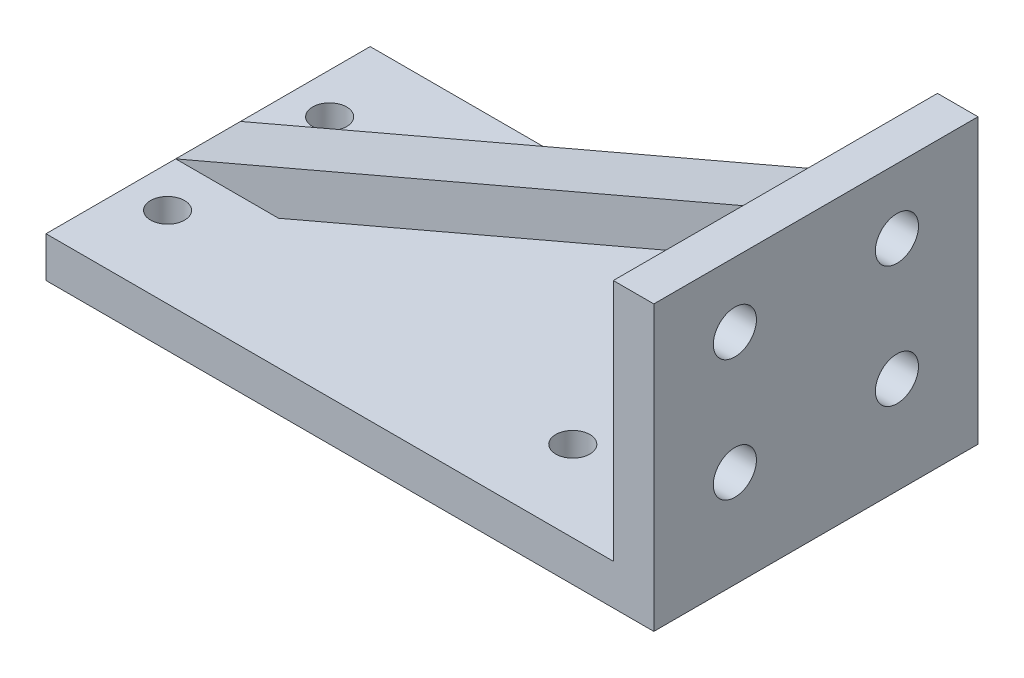
SolidWorks part; units mm, degrees
ref_plane "Front Plane" through (0, 0, 0) normal (0, 0, 1) x (1, 0, 0)
ref_plane "Top Plane" through (0, 0, 0) normal (0, 1, 0) x (1, 0, 0)
ref_plane "Right Plane" through (0, 0, 0) normal (1, 0, 0) x (0, 0, -1)
sketch "Sketch3" plane through (0, 0, 0) normal (0, 0, 1) x (1, 0, 0)
  line L0 (0, 6.35) -> (88.9, 44.45)
  line L1 (0, 0) -> (95.25, 0)
  line L2 (0, 0) -> (0, 6.35)
  line L3 (16.1201, 6.35) -> (88.9, 6.35)
  line L4 (95.25, 0) -> (95.25, 6.35)
  line L5 (95.25, 0) -> (88.9, 0)
  line L6 (95.25, 0) -> (95.25, 44.45)
  line L7 (95.25, 44.45) -> (88.9, 44.45)
  line L8 (88.9, 6.35) -> (88.9, 37.5414)
  line L9 (16.1201, 6.35) -> (88.9, 37.5414)
  line L10 (2.5014, 0.5134) -> (91.4014, 38.6134) construction
  dimension "D1" = 6.35
  dimension "D2" = 95.25
  dimension "D3" = 6.35
  dimension "D4" = 44.45
  dimension "D5" = 88.9
  dimension "D6" = 6.35
  dimension "D7" = 156.801
  dimension "D8" = 6.35
extrude "Boss-Extrude1" add sketch "Sketch3" along normal blind 50.8 contours L8 L3 L2 L1 L4 L6 L7 region at (44.8641, 24.4339, 0)
sketch "Sketch4" plane through (0, 0, 0) normal (0, -1, 0) x (1, 0, 0)
  line L0 (0, 50.8) -> (0, 0) construction
  line L1 (0, 0) -> (95.25, 0) construction
  line L2 (0, 50.8) -> (95.25, 50.8) construction
  circle A0 centre (6.35, 38.1) radius 2.667
  circle A1 centre (6.35, 12.7) radius 2.667
  circle A2 centre (69.85, 12.7) radius 2.667
  circle A3 centre (69.85, 38.1) radius 2.667
  dimension "D1" = 5.334
  dimension "D2" = 5.334
  dimension "D3" = 5.334
  dimension "D4" = 5.334
  dimension "D5" = 6.35
  dimension "D6" = 6.35
  dimension "D7" = 12.7
  dimension "D8" = 12.7
  dimension "D9" = 12.7
  dimension "D10" = 12.7
  dimension "D11" = 63.5
  dimension "D12" = 63.5
extrude "Cut-Extrude1" cut sketch "Sketch4" against normal through all
sketch "Sketch5" plane through (0, 0, 50.8) normal (0, 0, 1) x (1, 0, 0)
  line L1 (0, 6.35) -> (88.9, 6.35)
  line L2 (0, 6.35) -> (0, 44.45)
  line L3 (0, 44.45) -> (88.9, 44.45)
  line L4 (88.9, 6.35) -> (88.9, 44.45)
extrude "Cut-Extrude2" cut sketch "Sketch5" against normal blind 20.32
sketch "Sketch6" plane through (0, 0, 0) normal (0, 0, -1) x (-1, 0, 0)
  line L1 (-88.9, 44.45) -> (0, 44.45)
  line L2 (-88.9, 44.45) -> (-88.9, 6.35)
  line L3 (-88.9, 6.35) -> (0, 6.35)
  line L4 (0, 44.45) -> (0, 6.35)
extrude "Cut-Extrude3" cut sketch "Sketch6" against normal blind 20.32
sketch "Sketch7" plane through (95.25, 0, 0) normal (1, 0, 0) x (0, 0, -1)
  line L0 (-50.8, 0) -> (0, 0) construction
  line L1 (-50.8, 0) -> (-50.8, 44.45) construction
  line L2 (0, 0) -> (0, 44.45) construction
  circle A0 centre (-38.1, 15.24) radius 3.3782
  circle A1 centre (-12.7, 15.24) radius 3.3782
  circle A2 centre (-12.7, 34.29) radius 3.3782
  circle A3 centre (-38.1, 34.29) radius 3.3782
  dimension "D1" = 6.7564
  dimension "D2" = 6.7564
  dimension "D3" = 6.7564
  dimension "D4" = 6.7564
  dimension "D5" = 15.24
  dimension "D6" = 19.05
  dimension "D7" = 15.24
  dimension "D8" = 19.05
  dimension "D9" = 12.7
  dimension "D10" = 12.7
  dimension "D11" = 12.7
  dimension "D12" = 12.7
extrude "Cut-Extrude4" cut sketch "Sketch7" against normal through all
